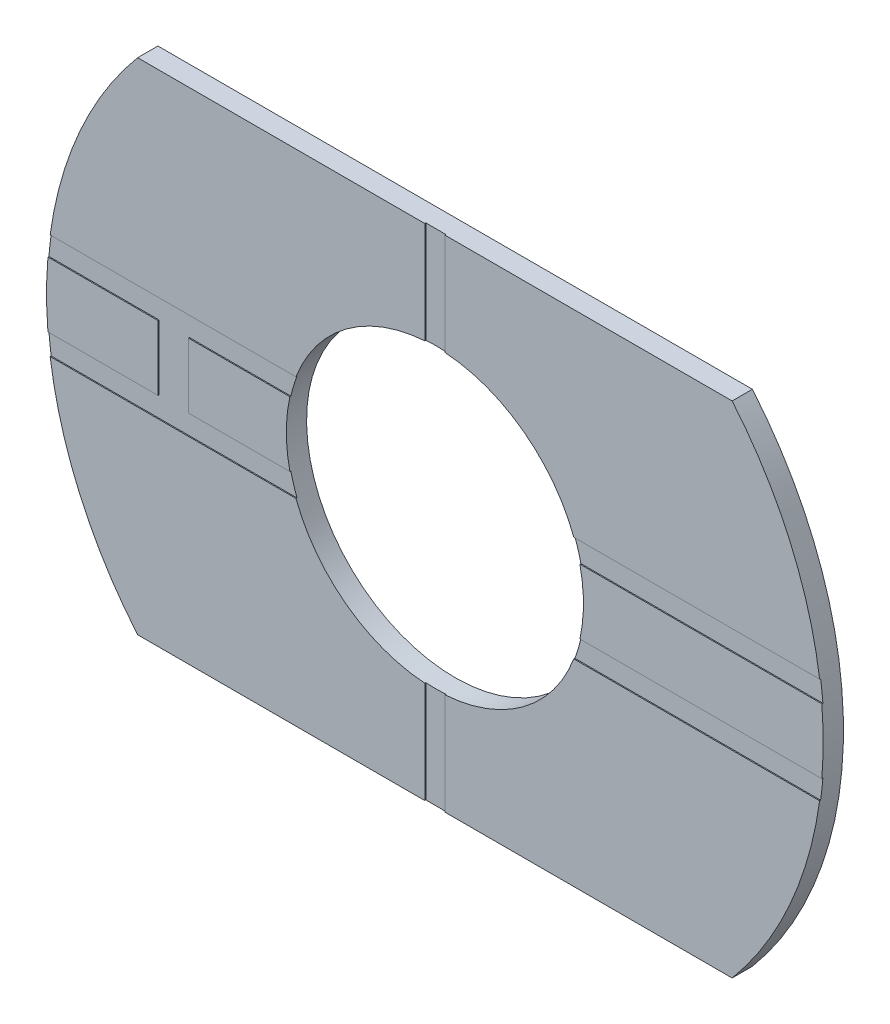
SolidWorks part; units mm, degrees
ref_plane "Спереди" through (0, 0, 0) normal (0, 0, 1) x (1, 0, 0)
ref_plane "Сверху" through (0, 0, 0) normal (0, 1, 0) x (1, 0, 0)
ref_plane "Справа" through (0, 0, 0) normal (1, 0, 0) x (0, 0, -1)
sketch "Эскиз1" plane through (0, 0, 0) normal (0, 0, 1) x (1, 0, 0)
  circle A0 centre (0, 0) radius 57.5
  circle A1 centre (0, 0) radius 22
  dimension "D1" = 44
  dimension "D2" = 115
extrude "Бобышка-Вытянуть1" add sketch "Эскиз1" along normal blind 3
sketch "Эскиз2" plane through (0, 0, 3) normal (0, 0, 1) x (1, 0, 0)
  line L1 (-71.6771, 37) -> (68.8401, 37)
  line L2 (-71.6771, 37) -> (-71.6771, 91.8379)
  line L3 (-71.6771, 91.8379) -> (68.8401, 91.8379)
  line L4 (68.8401, 37) -> (68.8401, 91.8379)
  line L5 (-71.6771, -94.4571) -> (68.8401, -94.4571)
  line L6 (-71.6771, -94.4571) -> (-71.6771, -37)
  line L7 (-71.6771, -37) -> (68.8401, -37)
  line L8 (68.8401, -94.4571) -> (68.8401, -37)
  dimension "D1" = 74
  dimension "D2" = 37
extrude "Вырез-Вытянуть1" cut sketch "Эскиз2" against normal through all
sketch "Эскиз3" plane through (0, 0, 3) normal (0, 0, 1) x (1, 0, 0)
  line L0 (-72.4233, -77.7327) -> (-21.3533, -77.7327) construction
  line L1 (-44.0142, 37) -> (44.0142, 37) construction
  line L2 (-1.5, 37) -> (1.5, 37)
  line L3 (-1.5, 37) -> (-1.5, 7.8)
  line L4 (-1.5, -37) -> (1.5, -37)
  line L5 (1.5, 37) -> (1.5, 7.8)
  line L6 (44.0142, -37) -> (-44.0142, -37) construction
  line L7 (1.5, 4.8) -> (1.5, -4.8)
  line L8 (-72.371, 7.8) -> (-1.5, 7.8)
  line L9 (-72.371, 7.8) -> (-72.371, 4.8)
  line L10 (-72.371, 4.8) -> (-41, 4.8)
  line L11 (63.7438, 7.8) -> (63.7438, 4.8)
  line L12 (65.5822, -4.8) -> (1.5, -4.8)
  line L13 (65.5822, -4.8) -> (65.5822, -7.8)
  line L14 (65.5822, -7.8) -> (1.5, -7.8)
  line L15 (-73.6341, -4.8) -> (-73.6341, -7.8)
  line L17 (-41, 4.8) -> (-41, -4.8)
  line L19 (-36.5, 4.8) -> (-36.5, -4.8)
  line L20 (-1.5, 4.8) -> (-1.5, -4.8)
  line L21 (1.5, 7.8) -> (63.7438, 7.8)
  line L22 (1.5, 4.8) -> (63.7438, 4.8)
  line L23 (-1.5, -4.8) -> (-36.5, -4.8)
  line L24 (-1.5, -7.8) -> (-73.6341, -7.8)
  line L25 (-1.5, -7.8) -> (-1.5, -37)
  line L26 (1.5, -7.8) -> (1.5, -37)
  line L27 (-36.5, 4.8) -> (-1.5, 4.8)
  line L28 (-41, -4.8) -> (-73.6341, -4.8)
  dimension "D1" = 3
  dimension "D2" = 1.5
  dimension "D3" = 3
  dimension "D4" = 3
  dimension "D5" = 4.8
  dimension "D6" = 4.8
  dimension "D7" = 35
  dimension "D8" = 4.5
extrude "Вырез-Вытянуть2" cut sketch "Эскиз3" against normal blind 0.15
